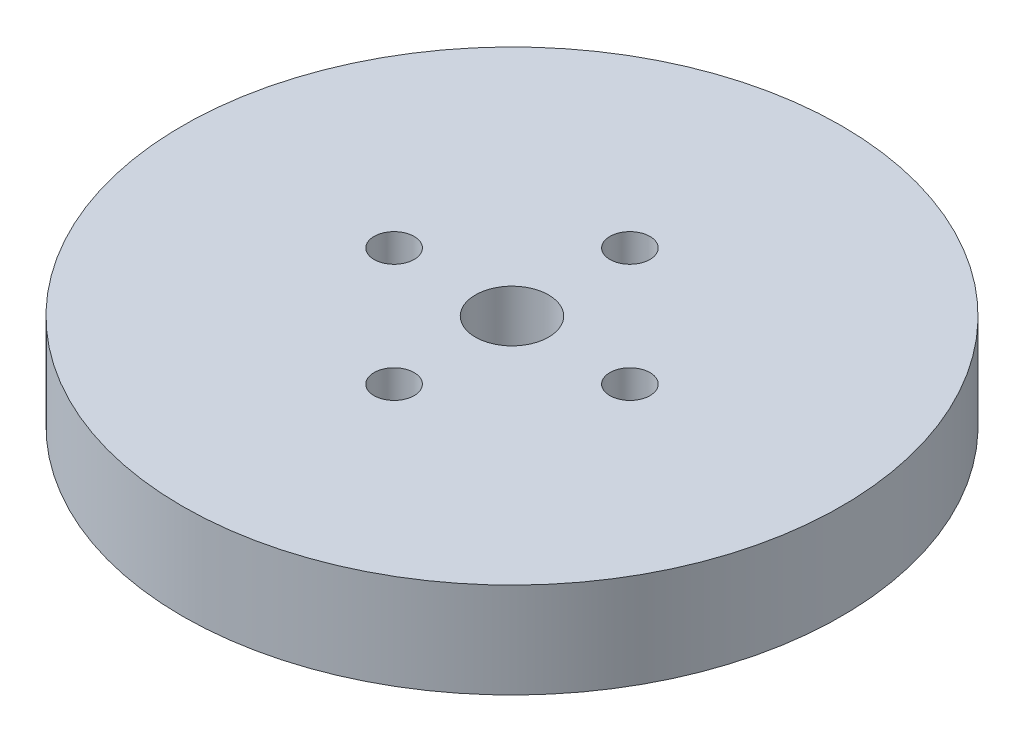
SolidWorks part; units mm, degrees
ref_plane "Front Plane" through (0, 0, 0) normal (0, 0, 1) x (1, 0, 0)
ref_plane "Top Plane" through (0, 0, 0) normal (0, 1, 0) x (1, 0, 0)
ref_plane "Right Plane" through (0, 0, 0) normal (1, 0, 0) x (0, 0, -1)
sketch "Sketch1" plane through (0, 0, 0) normal (0, 1, 0) x (1, 0, 0)
  circle A0 centre (0, 0) radius 90
  dimension "FLANGE_OD" = 180
extrude "Boss-Extrude1" add sketch "Sketch1" along normal blind 26
sketch "Sketch2" plane through (0, 0, 0) normal (0, 1, 0) x (1, 0, 0)
  circle A0 centre (0, 0) radius 10
  dimension "BORE_D" = 20
extrude "Cut-Extrude1" cut sketch "Sketch2" along normal through all
sketch "Sketch3" plane through (0, 26, 0) normal (0, 1, 0) x (1, 0, 0)
  circle A0 centre (0, 0) radius 32.2013 construction
  circle A1 centre (-32.2013, 0) radius 5.4708
  dimension "BOLT_D" = 10.9416
  dimension "BOLT_PCD" = 64.4026
extrude "Cut-Extrude2" cut sketch "Sketch3" against normal blind 19.1569
pattern_circular "CirPattern1" count 4 over 360 about axis through (0, 0, 0) along (0, 1, 0) of "Cut-Extrude2"
